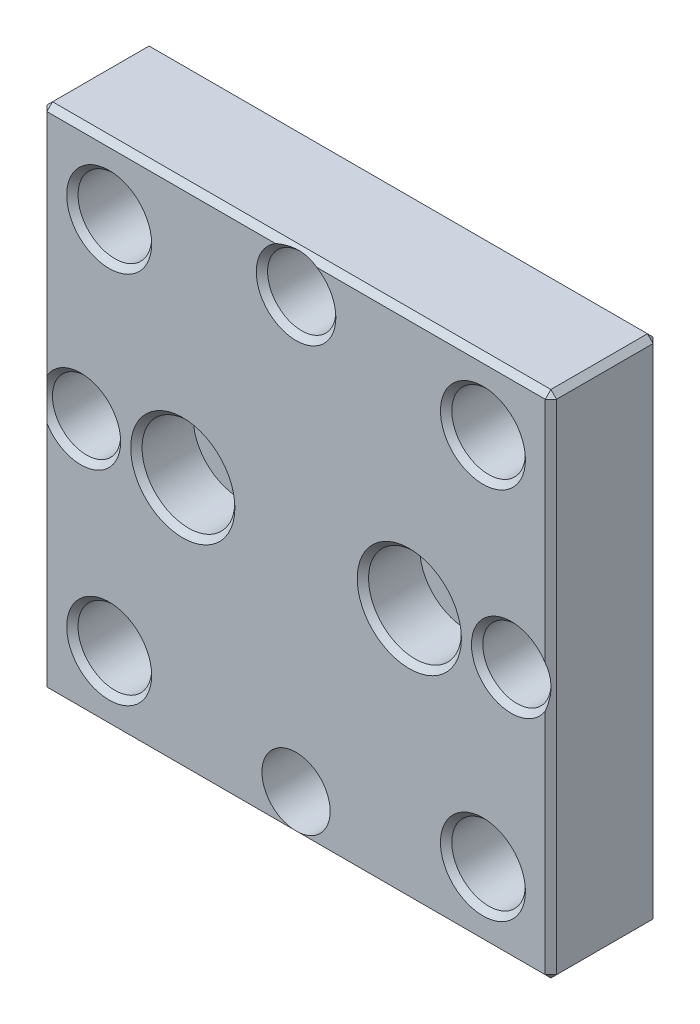
SolidWorks part; units mm, degrees
ref_plane "Front Plane" through (0, 0, 0) normal (0, 0, 1) x (1, 0, 0)
ref_plane "Top Plane" through (0, 0, 0) normal (0, 1, 0) x (1, 0, 0)
ref_plane "Right Plane" through (0, 0, 0) normal (1, 0, 0) x (0, 0, -1)
sketch "Sketch1" plane through (0, 0, 0) normal (0, 0, 1) x (1, 0, 0)
  line L1 (0, 0) -> (45, 0)
  line L2 (0, 0) -> (0, 45)
  line L3 (0, 45) -> (45, 45)
  line L4 (45, 0) -> (45, 45)
  circle A0 centre (22.5, 22.5) radius 15.125 construction
  circle A1 centre (12.5, 22.5) radius 2.2
  circle A2 centre (32.5, 22.5) radius 2.2
  circle A3 centre (12.5, 22.5) radius 4.1
  circle A4 centre (32.5, 22.5) radius 4.1
  dimension "D5" = 30.25
  dimension "D6" = 4.4
  dimension "D7" = 4.4
  dimension "D10" = 8.2
  dimension "D11" = 8.2
  dimension "D1" = 45
  dimension "D2" = 45
  dimension "D3" = 22.5
  dimension "D4" = 22.5
  dimension "D8" = 10
  dimension "D9" = 10
extrude "Boss-Extrude1" add sketch "Sketch1" along normal blind 9.525 contours L1 L4 L3 L2 A4 A3 region at (22.5, 22.5, 0)
extrude "Boss-Extrude2" add sketch "Sketch1<3>" along normal blind 4.5 contours A3 A1 | A4 A2 region at (8.516, 22.5, 0) region at (28.516, 22.5, 0)
sketch "Sketch1<3>" plane through (0, 0, 0) normal (0, 0, 1) x (1, 0, 0) same geometry as "Sketch1"
sketch "Sketch3" plane through (0, 0, 9.525) normal (0, 0, 1) x (1, 0, 0)
  line L0 (0, 45) -> (45, 45) construction
  line L1 (0, 0) -> (0, 45) construction
  line L2 (0, 0) -> (45, 0) construction
  line L3 (45, 0) -> (45, 45) construction
  circle A0 centre (22.5, 41.5) radius 3.0127
  circle A1 centre (3.5, 22.5) radius 3.0127
  circle A2 centre (41.5, 22.5) radius 3.0127
  circle A3 centre (22.5, 3.5) radius 3.0127
  dimension "D6" = 6.0254
  dimension "D7" = 6.0254
  dimension "D8" = 6.0254
  dimension "D9" = 6.0254
  dimension "D1" = 22.5
  dimension "D2" = 22.5
  dimension "D3" = 22.5
  dimension "D4" = 22.5
  dimension "D5" = 3.5
  dimension "D10" = 3.5
  dimension "D11" = 3.5
  dimension "D12" = 3.5
extrude "Cut-Extrude1" cut sketch "Sketch3" against normal through all
sketch "Sketch5" plane through (0, 0, 9.525) normal (0, 0, 1) x (1, 0, 0)
  line L0 (0, 45) -> (45, 45) construction
  line L1 (0, 0) -> (0, 45) construction
  circle A0 centre (6, 39) radius 3.2512
  circle A1 centre (39, 39) radius 3.2512
  circle A2 centre (39, 6) radius 3.2512
  circle A3 centre (6, 6) radius 3.2512
  dimension "D1" = 6.5024
  dimension "D2" = 6.5024
  dimension "D3" = 6.5024
  dimension "D4" = 6.5024
  dimension "D5" = 6
  dimension "D6" = 6
  dimension "D7" = 33
  dimension "D8" = 33
extrude "Cut-Extrude2" cut sketch "Sketch5" against normal blind 6.4008
sketch "Sketch6" plane through (0, 0, 9.525) normal (0, 0, 1) x (1, 0, 0)
  line L1 (0, 0) -> (0, 45) construction
  circle A0 centre (6, 39) radius 1.25
  circle A1 centre (39, 39) radius 1.25
  circle A2 centre (39, 6) radius 1.25
  circle A3 centre (6, 6) radius 1.25
  dimension "D1" = 2.5
  dimension "D2" = 2.5
  dimension "D3" = 2.5
  dimension "D4" = 2.5
  dimension "D5" = 33
  dimension "D6" = 6
  dimension "D7" = 33
  dimension "D8" = 33
  dimension "D9" = 33
  dimension "D10" = 6
extrude "Cut-Extrude3" cut sketch "Sketch6" against normal through all
sketch "Sketch7" plane through (0, 0, 0) normal (0, 0, -1) x (-1, 0, 0)
  line L0 (0, 0) -> (-45, 0) construction
  line L1 (-13.65, 22.5) -> (-31.35, 22.5)
  line L2 (-13.65, 22.5) -> (-13.65, -17.5)
  line L3 (-13.65, -17.5) -> (-31.35, -17.5)
  line L4 (-31.35, 22.5) -> (-31.35, -17.5)
  circle A0 centre (-22.5, 22.5) radius 15.3
  circle A1 centre (-3.5, 22.5) radius 3.0127 construction
  circle M15 centre (-22.5, 3.5) radius 3.0127
  line M19 (-45, 0) -> (0, 0)
  line M22 (-45, 45) -> (-45, 0)
  circle M23 centre (-12.5, 22.5) radius 2.2
  circle M24 centre (-32.5, 22.5) radius 2.2
  circle M27 centre (-39, 6) radius 1.25
  dimension "D1" = 30.6
  dimension "D2" = 22.5
  dimension "D3" = 22.5
  dimension "D4" = 17.7
  dimension "D5" = 40
  dimension "D6" = 8.85
  dimension "D7" = 40
  dimension "D8" = 90
extrude "Cut-Extrude4" cut sketch "Sketch7" against normal blind 3.5 contours A0 L4 L2 M22 M19 M27 | L4 A0 L2 L1 M24 | L2 A0 L4 L1 M24 M23 | A0 L4 L2 M19 M15 region at (22.5, 26.5592, 0) region at (22.5, 15.2056, 0) region at (22.5, 6.9966, 0)
chamfer "Chamfer1" distance 0.5 angle 45 36 edges at (36.6, 22.5, 9.525) (16.6, 22.5, 9.525) (6.5127, 22.5, 9.525) (9.2512, 6, 9.525) (42.2512, 6, 9.525) (44.5127, 22.5, 9.525) (42.2512, 39, 9.525) (25.5127, 41.5, 9.525) (9.2512, 39, 9.525) (7.25, 39, 0) (40.25, 39, 0) (40.25, 6, 0) (44.5127, 22.5, 0) (19.4873, 3.5, 3.5) (7.25, 6, 0) (6.5127, 22.5, 0) (25.5127, 41.5, 0) (45, 22.5, 9.525) (22.5, 45, 9.525) (45, 45, 4.7625) (45, 0, 4.7625) (22.5, 0, 9.525) (0, 22.5, 9.525) (0, 45, 4.7625) (0, 0, 4.7625) (0, 22.5, 0) (22.5, 45, 0) (45, 22.5, 0) (31.35, 0, 1.75) (22.5, 0, 3.5) (13.65, 0, 1.75) (6.825, 0, 0) (38.175, 0, 0) (31.35, 5.0097, 0) (13.65, 5.0097, 0) (22.5, 37.8, 0)
